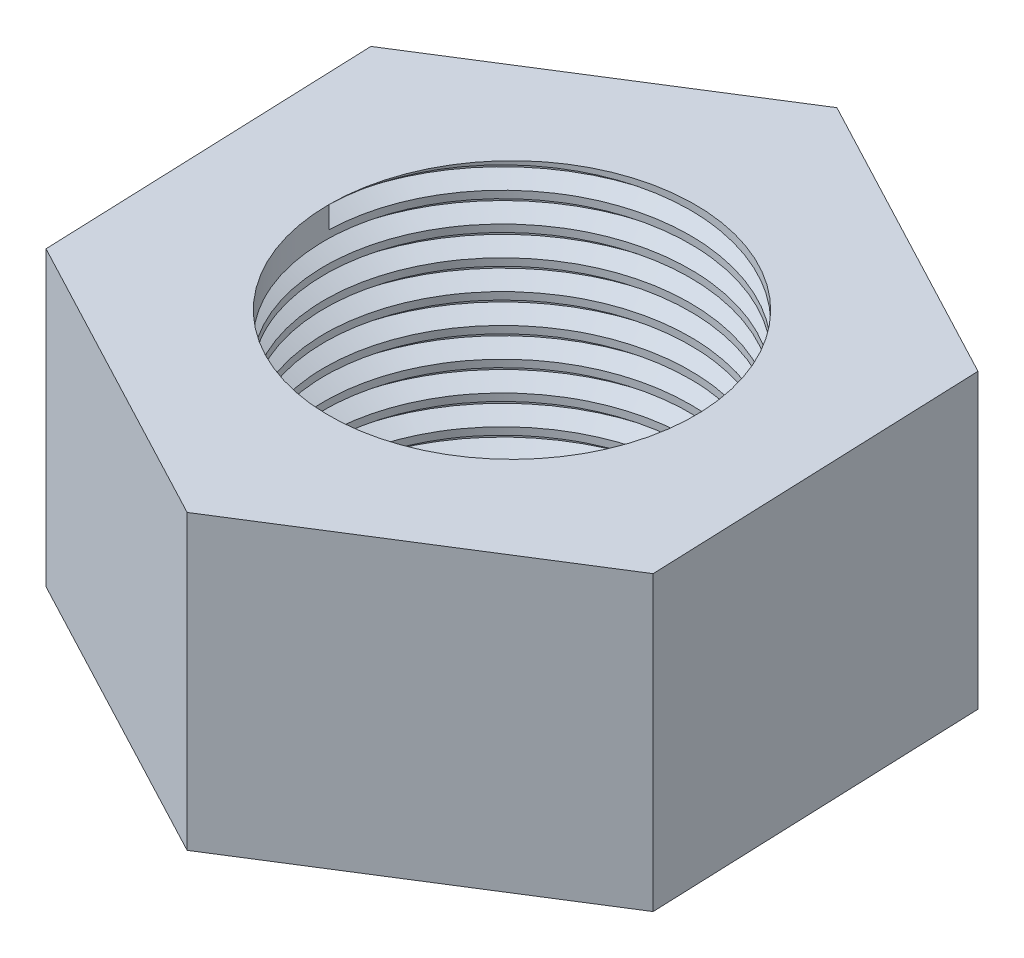
SolidWorks part; units mm, degrees
ref_plane "Ebene vorne" through (0, 0, 0) normal (0, 0, 1) x (1, 0, 0)
ref_plane "Ebene oben" through (0, 0, 0) normal (0, 1, 0) x (1, 0, 0)
ref_plane "Ebene rechts" through (0, 0, 0) normal (1, 0, 0) x (0, 0, -1)
sketch "Skizze1" plane through (0, 0, 0) normal (0, 1, 0) x (1, 0, 0)
  line L1 (4.0848, -2.1559) -> (3.9094, 2.4596)
  line L2 (3.9094, 2.4596) -> (-0.1754, 4.6155)
  line L3 (-0.1754, 4.6155) -> (-4.0848, 2.1559)
  line L4 (-4.0848, 2.1559) -> (-3.9094, -2.4596)
  line L5 (-3.9094, -2.4596) -> (0.1754, -4.6155)
  line L6 (0.1754, -4.6155) -> (4.0848, -2.1559)
  circle A0 centre (0, 0) radius 4 construction
  dimension "D1" = 8
extrude "Aufsatz-Linear austragen1" add sketch "Skizze1" along normal blind 4
sketch "Skizze2" plane through (0, 0, 0) normal (0, -1, 0) x (1, 0, 0)
  circle A0 centre (0, 0) radius 2.5
  dimension "D1" = 5
extrude "Schnitt-Linear austragen1" cut sketch "Skizze2" against normal blind 4
thread "Gewinde1" pitch 0.4 method cut profile "Gewindeprofil1" start angle 0, offset 0, length 0, pitch 0.4, diameter 5
ref_plane "Ebene1" through (-2.5, 4, 0) normal (0, 0, 1) x (-1, 0, 0)
sketch "Gewindeprofil1" plane through (-2.5, 4, 0) normal (0, 0, 1) x (-1, 0, 0)
  line L0 (0, 0) -> (0, 0.4) construction
  line L1 (0, 0) -> (0.2165, 0.125)
  line L2 (0.2165, 0.125) -> (0.2165, 0.175)
  line L3 (0.2165, 0.175) -> (0, 0.3)
  line L4 (0.2165, 0.15) -> (0, 0.15) construction
  line L11 (0, 0) -> (0, 0.3)
  point P2 (0, 0)
  dimension "Pitch" = 0.4
  dimension "Profile_Angle" = 60
  dimension "Profile_Land" = 0.05
  dimension "Profile_Height" = 0.2165
